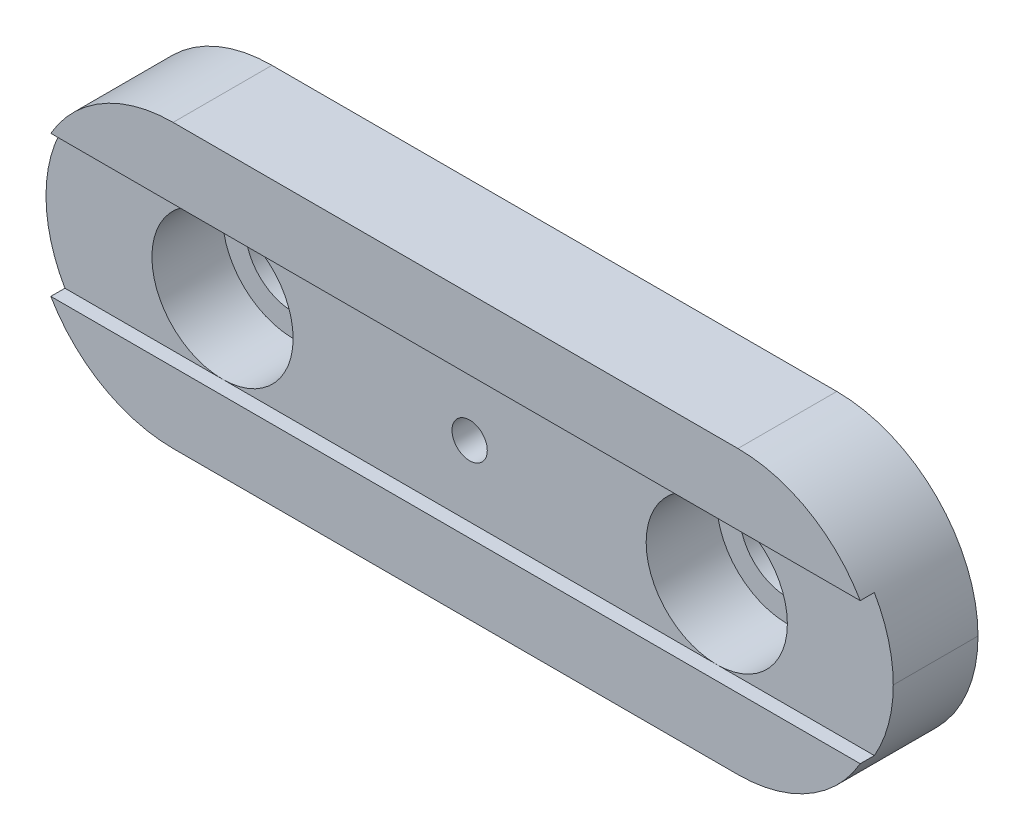
SolidWorks part; units mm, degrees
ref_plane "前视基准面" through (0, 0, 0) normal (0, 0, 1) x (1, 0, 0)
ref_plane "上视基准面" through (0, 0, 0) normal (0, 1, 0) x (1, 0, 0)
ref_plane "右视基准面" through (0, 0, 0) normal (1, 0, 0) x (0, 0, -1)
sketch "草图1" plane through (0, 0, 0) normal (0, 0, 1) x (1, 0, 0)
  line L1 (-60, -20) -> (60, -20)
  line L2 (-60, -20) -> (-60, 20)
  line L3 (-60, 20) -> (60, 20)
  line L4 (60, -20) -> (60, 20)
  line L5 (-60, -20) -> (60, 20) construction
  line L6 (-60, 20) -> (60, -20) construction
  point P0 (0, 0)
  dimension "D1" = 40
  dimension "D2" = 120
extrude "凸台-拉伸1" add sketch "草图1" along normal blind 14
sketch "草图2" plane through (0, 0, 14) normal (0, 0, 1) x (1, 0, 0)
  line L0 (60, -20) -> (60, 20) construction
  line L1 (-60, -10) -> (60, -10)
  line L2 (-60, -10) -> (-60, 10)
  line L3 (-60, 10) -> (60, 10)
  line L4 (60, -10) -> (60, 10)
  line L5 (-60, -10) -> (60, 10) construction
  line L6 (-60, 10) -> (60, -10) construction
  point P0 (0, 0)
  dimension "D1" = 20
extrude "切除-拉伸1" cut sketch "草图2" against normal blind 2
hole_wizard "M12 六角头螺栓的柱形沉头孔1" positions "草图4" profile "草图3" counterbore size "M12" standard "GB" end condition through all
sketch "草图4" plane through (0, 0, 12) normal (0, 0, 1) x (1, 0, 0)
  point P0 (-35, 0)
  point P1 (35, 0)
  dimension "D1" = 70
  dimension "D2" = 35
sketch "草图3" plane through (-35, 0, 12) normal (1, 0, 0) x (0, -1, 0)
  line L0 (0, 0) -> (0, 12)
  line L1 (0, 12) -> (6.75, 12)
  line L3 (6.75, 12) -> (6.75, 10)
  line L4 (6.75, 10) -> (10, 10)
  line L5 (10, 10) -> (10, 0)
  line L7 (10, 0) -> (0, 0)
  line L11 (0, -6.35) -> (0, 107.95) construction
  dimension "通孔孔直径" = 13.5
  dimension "通孔孔深度" = 12
  dimension "柱形沉头孔直径" = 20
  dimension "柱形沉头孔深度" = 10
sketch "草图5" plane through (0, 0, 14) normal (0, 0, 1) x (1, 0, 0)
  circle A0 centre (-35, 0) radius 10 construction
  circle A1 centre (-35, 0) radius 10
  circle A2 centre (35, 0) radius 10 construction
  circle A3 centre (35, 0) radius 10
extrude "切除-拉伸2" [suppressed] cut sketch "草图5" against normal blind 2
fillet "圆角1" radius 20 4 edges at (60, 20, 7) (60, -20, 7) (-60, -20, 7) (-60, 20, 7)
hole_wizard "M6 螺纹孔1" positions "草图7" profile "草图8" tap size "M6" standard "GB" end condition through all
sketch "草图7" plane through (0, 0, 12) normal (0, 0, 1) x (1, 0, 0)
  point P0 (0, 0)
sketch "草图8" plane through (0, 0, 12) normal (1, 0, 0) x (0, -1, 0)
  line L0 (0, 0) -> (0, 12)
  line L1 (0, 12) -> (2.5, 12)
  line L2 (2.5, 12) -> (2.5, 0)
  line L5 (2.5, 0) -> (0, 0)
  line L11 (0, -6.35) -> (0, 107.95) construction
  dimension "通孔螺纹孔钻头直径" = 5
  dimension "通孔螺纹孔钻头深度" = 12
cosmetic thread "孔螺蚊线1" parameters "D2"=6
